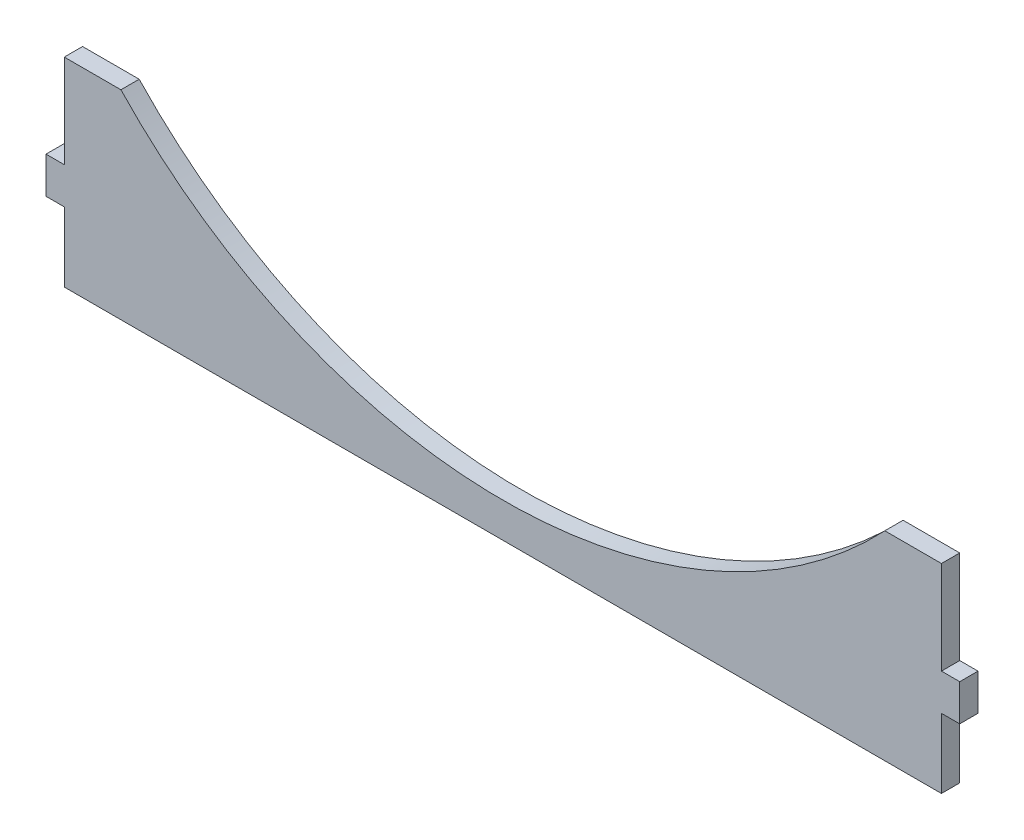
SolidWorks part; units mm, degrees
ref_plane "Plan de face" through (0, 0, 0) normal (0, 0, 1) x (1, 0, 0)
ref_plane "Plan de dessus" through (0, 0, 0) normal (0, 1, 0) x (1, 0, 0)
ref_plane "Plan de droite" through (0, 0, 0) normal (1, 0, 0) x (0, 0, -1)
sketch "Esquisse1" plane through (0, 0, 0) normal (0, 0, 1) x (1, 0, 0)
  line L0 (0, 0) -> (-15.5, 0)
  line L1 (-15.5, 0) -> (-15.5, -25.5)
  line L2 (-15.5, -25.5) -> (-20.5, -25.5)
  line L3 (-20.5, -25.5) -> (-20.5, -35.5)
  line L4 (-20.5, -35.5) -> (-15.5, -35.5)
  line L5 (-15.5, -35.5) -> (-15.5, -54.5)
  line L6 (-15.5, -54.5) -> (224.5, -54.5)
  line L7 (224.5, -54.5) -> (224.5, -35.5)
  line L8 (224.5, -35.5) -> (229.5, -35.5)
  line L9 (229.5, -35.5) -> (229.5, -25.5)
  line L10 (229.5, -25.5) -> (224.5, -25.5)
  line L11 (224.5, -25.5) -> (224.5, 0)
  line L12 (224.5, 0) -> (209, 0)
  arc A0 (209, 0) -> (0, 0) centre (104.5, 98.8361) cw
  point P17 (104.5, -45)
  dimension "D1" = 15.5
  dimension "D2" = 5
  dimension "D3" = 25.5
  dimension "D4" = 10
  dimension "D5" = 19
  dimension "D6" = 240
  dimension "D7" = 9.5
extrude "Boss.-Extru.1" add sketch "Esquisse1" along normal blind 5
